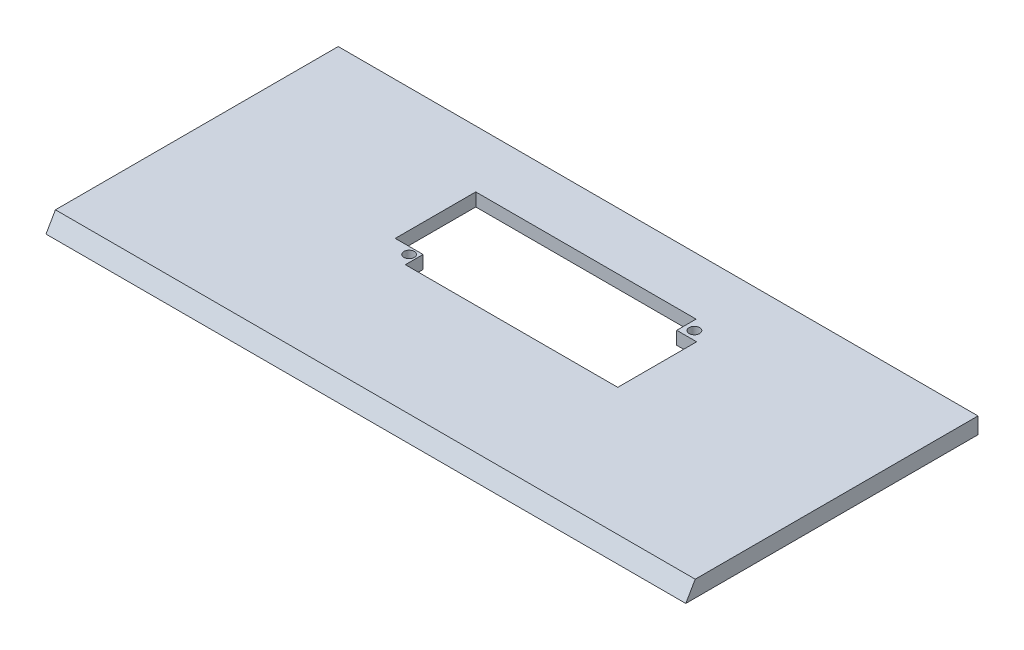
SolidWorks part; units mm, degrees
ref_plane "Alzado" through (0, 0, 0) normal (0, 0, 1) x (1, 0, 0)
ref_plane "Planta" through (0, 0, 0) normal (0, 1, 0) x (1, 0, 0)
ref_plane "Vista lateral" through (0, 0, 0) normal (1, 0, 0) x (0, 0, -1)
sketch "Croquis1" plane through (0, 0, 0) normal (1, 0, 0) x (0, 0, -1)
  line L0 (0, 0) -> (89.52, 0)
  line L1 (89.52, 0) -> (89.52, 5)
  line L2 (89.52, 5) -> (2.8868, 5)
  line L3 (0, 0) -> (2.8868, 5)
  dimension "D1" = 89.52
  dimension "D2" = 5
  dimension "D3" = 120
extrude "Saliente-Extruir1" add sketch "Croquis1" along normal blind 196
shell "Vaciado1" thickness 4 removed face at (98, 0, -44.76)
sketch "Sketch1" plane through (0, 1, 0) normal (0, -1, 0) x (-1, 0, 0)
  line L0 (0, 89.52) -> (-196, 89.52) construction
  line L1 (-98, 89.52) -> (-98, -14.2345)
sketch "Sketch2" plane through (0, 1, 0) normal (0, -1, 0) x (-1, 0, 0)
  line L0 (-59.6372, 47.3551) -> (-68.1615, 47.3551)
  line L5 (-68.1615, 47.3551) -> (-68.1615, 41.923)
  line L6 (-68.1615, 41.923) -> (-133.2369, 41.923)
  line L7 (-133.2369, 41.923) -> (-133.2369, 66.0933)
  line L8 (-133.2369, 66.0933) -> (-127.1352, 66.0933)
  line L9 (-127.1352, 66.0933) -> (-127.1352, 72.023)
  line L10 (-127.1352, 72.023) -> (-59.6372, 72.023)
  line L11 (-59.6372, 72.023) -> (-59.6372, 47.3551)
  circle A0 centre (-66.0169, 45.223) radius 1.6
  circle A1 centre (-129.9169, 68.723) radius 1.6
  point P4 (-97.9669, 56.973)
extrude "Cut-Extrude1" cut sketch "Sketch2" against normal blind 4.9
